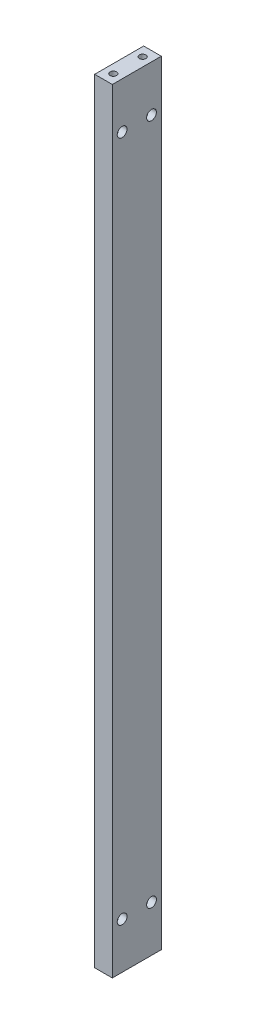
SolidWorks part; units mm, degrees
material "Beech"
ref_plane "Front Plane" through (0, 0, 0) normal (0, 0, 1) x (1, 0, 0)
ref_plane "Top Plane" through (0, 0, 0) normal (0, 1, 0) x (1, 0, 0)
ref_plane "Right Plane" through (0, 0, 0) normal (1, 0, 0) x (0, 0, -1)
sketch "Sketch1" plane through (0, 0, 0) normal (0, 1, 0) x (1, 0, 0)
  line L1 (0, 0) -> (18, 0)
  line L2 (0, 0) -> (0, 50)
  line L3 (0, 50) -> (18, 50)
  line L4 (18, 0) -> (18, 50)
  dimension "D1" = 18
  dimension "D2" = 50
extrude "base" add sketch "Sketch1" along normal blind 789.8
hole_wizard "end bolt holes for inserts" positions "Sketch2" profile "Sketch3" hole size "M6" standard "ANSI Metric"
sketch "Sketch2" plane through (0, 0, 0) normal (0, -1, 0) x (-1, 0, 0)
  line L1 (-9, 50) -> (-9, 0)
  line L2 (-18, 50) -> (0, 50) construction
  line L3 (0, 0) -> (-18, 0) construction
  line L4 (-9, 10) -> (-18, 25)
  line L5 (-18, 0) -> (-18, 50) construction
  line L6 (-18, 25) -> (-9, 40)
  point P10 (-9, 40)
  point P12 (-9, 10)
  dimension "D1" = 30
sketch "Sketch3" plane through (9, 0, -40) normal (1, 0, 0) x (0, 0, -1)
  line L0 (0, 0) -> (0, 58.9828)
  line L1 (0, 58.9828) -> (3.3, 57)
  line L2 (3.3, 57) -> (3.3, 0)
  line L5 (3.3, 0) -> (0, 0)
  line L10 (0, 58.9828) -> (-3.3, 57) construction
  line L11 (0, -6.35) -> (0, 107.95) construction
  dimension "Hole Dia." = 6.6
  dimension "Hole Depth" = 57
  dimension "Drill Angle" = 118
ref_axis "bottom bolt hole axis" through (9, 57, -10) along (0, -1, 0)
ref_axis "top bolt hole axis" through (9, 57, -40) along (0, -1, 0)
hole_wizard "cross dowel bolt clearance holes" positions "Sketch4" profile "Sketch5" hole size "Ø10.0" standard "ANSI Metric" end condition through all
sketch "Sketch4" plane through (0, 0, 0) normal (-1, 0, 0) x (0, 0, 1)
  line L0 (-40, 57) -> (-40, 0) construction
  line L1 (-10, 57) -> (-10, 0) construction
  line L2 (-13.3, 57) -> (-6.7, 57) construction
  line L3 (-13.3, 57) -> (-6.7, 57)
  point P0 (-40, 47)
  point P4 (-10, 47)
  dimension "D1" = 10
sketch "Sketch5" plane through (0, 47, -40) normal (0, 1, 0) x (0, 0, 1)
  line L0 (0, 0) -> (0, 18)
  line L1 (0, 18) -> (5, 18)
  line L2 (5, 18) -> (5, 0)
  line L5 (5, 0) -> (0, 0)
  line L11 (0, -6.35) -> (0, 107.95) construction
  dimension "Thru Hole Dia." = 10
  dimension "Thru Hole Depth" = 18
ref_plane "midplane along length" through (0, 394.9, 0) normal (0, -1, 0) x (-1, 0, 0)
mirror "mirror end bolt holes" about plane through (0, 394.9, 0) normal (0, -1, 0) of "cross dowel bolt clearance holes", "end bolt holes for inserts"
equation "\"board_thickness\"= 18mm"
equation "\"way_width\"= 75mm"
equation "\"way_thickness\"= 50mm"
equation "\"radial_clearance\"= 0.1mm"
equation "\"slider_width\"= \"way_width\"-2* \"radial_clearance\" - 2*0.65"
equation "\"slider_thickness\"= \"way_thickness\" - 2 * \"radial_clearance\""
equation "\"column_width\"= \"way_width\" + 2 * \"board_thickness\""
equation "\"boxway_slot_width\"= 50mm"
equation "\"keeper_rail_width\"= (\"column_width\" - \"boxway_slot_width\")/2"
equation "\"slider_length\"= 125mm"
equation "\"nut_diameter\"= 22mm"
equation "\"nut_length\"= 15mm"
equation "\"leadscrew_diameter\"= 10mm"
equation "\"leadscrew_radial_clearance\"= 1mm"
equation "\"bearing_bolt_pattern_width\"= 30mm"
equation "\"bearing_bolt_pattern_height\"= 75mm"
equation "\"desktop_bolt_pattern_width\"= 30mm"
equation "\"desktop_bolt_pattern_height\"= 30mm"
equation "\"bearing_bolt_nut_counterbore_diameter\"= 12mm"
equation "\"bearing_bolt_nut_counterbore_depth\"= 10mm"
equation "\"desktop_depth\"= 500mm"
equation "\"desktop_width\"= 650mm"
equation "\"desktop_thickness\"= 18mm"
equation "\"leg_height\"=100mm"
equation "\"leg_width\"=18mm"
equation "\"leg_length\"=500mm"
equation "\"lap_joint_height\"= 50mm"
equation "\"lap_dowel_diameter\"= 8mm"
equation "\"lap_dowel_hole_z_spacing\"=30"
equation "\"D1@Sketch1\"=\"board_thickness\""
equation "\"D2@Sketch1\"=\"lap_joint_height\""
equation "\"D1@Sketch2\"=\"lap_dowel_hole_z_spacing\""
